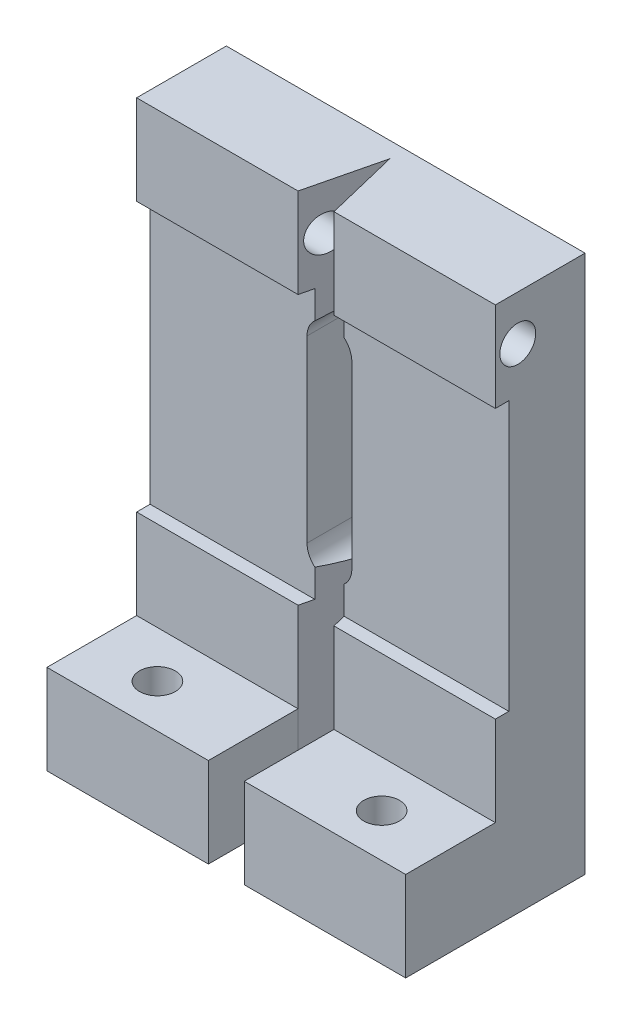
SolidWorks part; units mm, degrees
ref_plane "Front Plane" through (0, 0, 0) normal (0, 0, 1) x (1, 0, 0)
ref_plane "Top Plane" through (0, 0, 0) normal (0, 1, 0) x (1, 0, 0)
ref_plane "Right Plane" through (0, 0, 0) normal (1, 0, 0) x (0, 0, -1)
sketch "Sketch1" plane through (0, 0, 0) normal (0, 0, 1) x (1, 0, 0)
  line L1 (0, 0) -> (-40, 0)
  line L2 (0, 0) -> (0, -60)
  line L3 (0, -60) -> (-40, -60)
  line L4 (-40, 0) -> (-40, -60)
  dimension "D1" = 40
  dimension "D2" = 60
extrude "Boss-Extrude1" add sketch "Sketch1" along normal blind 10
sketch "Sketch2" plane through (0, 0, 10) normal (0, 0, 1) x (1, 0, 0)
  line L0 (-20, -15) -> (-20, -35) construction
  line L1 (-17.5, -15) -> (-17.5, -35)
  line L2 (-22.5, -15) -> (-22.5, -35)
  line L3 (0, -60) -> (0, 0) construction
  line L4 (-40, -60) -> (0, -60) construction
  arc A0 (-17.5, -15) -> (-22.5, -15) centre (-20, -15) ccw
  arc A1 (-22.5, -35) -> (-17.5, -35) centre (-20, -35) ccw
  point P2 (-20, -25)
  dimension "D1" = 5
  dimension "D2" = 20
  dimension "D3" = 20
  dimension "D4" = 35
extrude "Cut-Extrude1" cut sketch "Sketch2" against normal through all
sketch "Sketch5" plane through (0, 0, 0) normal (1, 0, 0) x (0, 0, -1)
  line L0 (-8.5, -10) -> (-10, -10)
  line L1 (-10, -60) -> (-10, 0) construction
  line L2 (-8.5, -10) -> (-8.5, -40)
  line L3 (-10, -60) -> (0, -60) construction
  line L4 (-8.5, -40) -> (-10, -40)
  line L7 (-10, -10) -> (-10, -40)
  dimension "D1" = 1.5
  dimension "D4" = 30
  dimension "D5" = 20
extrude "Cut-Extrude4" cut sketch "Sketch5" against normal through all
sketch "Sketch6" plane through (0, 0, 10) normal (0, 0, 1) x (1, 0, 0)
  line L0 (-40, -40) -> (-40, -60) construction
  line L1 (0, -60) -> (-40, -60)
  line L2 (0, -60) -> (0, -50)
  line L3 (0, -50) -> (-40, -50)
  line L4 (-40, -60) -> (-40, -50)
  dimension "D1" = 10
extrude "Boss-Extrude2" add sketch "Sketch6" along normal blind 10
sketch "Sketch7" plane through (0, -50, 0) normal (0, 1, 0) x (1, 0, 0)
  line L3 (-40, -20) -> (-40, -10) construction
  circle A0 centre (-7.5, -15.1829) radius 2
  circle A1 centre (-32.5, -15.1829) radius 2
  dimension "D1" = 4
  dimension "D2" = 4
  dimension "D3" = 7.5
  dimension "D5" = 25
extrude "Cut-Extrude5" cut sketch "Sketch7" against normal blind 40
sketch "Sketch8" plane through (0, 0, 0) normal (0, 1, 0) x (1, 0, 0)
  line L0 (-22, -10) -> (-20, -1.7721)
  line L1 (-17.5, 0) -> (-17.5, -8.5) construction
  line L2 (-20, -1.7721) -> (-18, -10)
  line L3 (0, -10) -> (-40, -10) construction
  line L4 (-22.5, 0) -> (-22.5, -8.5) construction
  line L5 (-22, -10) -> (-22, -20)
  line L6 (-17.5, 0) -> (-17.5, -8.5) construction
  line L7 (0, -20) -> (-40, -20) construction
  line L8 (-22, -20) -> (-18, -20)
  line L9 (-18, -20) -> (-18, -10)
  dimension "D1" = 0.5
  dimension "D2" = 2.5
  dimension "D3" = 0.5
extrude "Cut-Extrude7" cut sketch "Sketch8" against normal up to surface (60 mm away) up to face at (-32.5, -60, 17.1829)
sketch "Sketch9" plane through (0, -60, 0) normal (0, -1, 0) x (1, 0, 0)
  line L3 (0, 20) -> (0, 0) construction
  line L5 (-40, 8.5) -> (-21.6354, 8.5) construction
  circle A0 centre (-32.5, 6.5) radius 2
  circle A1 centre (-7.5, 6.5) radius 2
  dimension "D1" = 4
  dimension "D3" = 7.5
  dimension "D4" = 4
  dimension "D2" = 25
extrude "Cut-Extrude9" cut sketch "Sketch9" against normal blind 15
sketch "Sketch10" plane through (0, 0, 0) normal (1, 0, 0) x (0, 0, -1)
  line L1 (-10, 0) -> (0, 0) construction
  line L2 (-10, -10) -> (-10, 0) construction
  circle A0 centre (-7.5, -5) radius 2
  dimension "D1" = 4
  dimension "D2" = 5
  dimension "D3" = 2.5
extrude "Cut-Extrude10" cut sketch "Sketch10" against normal blind 30
